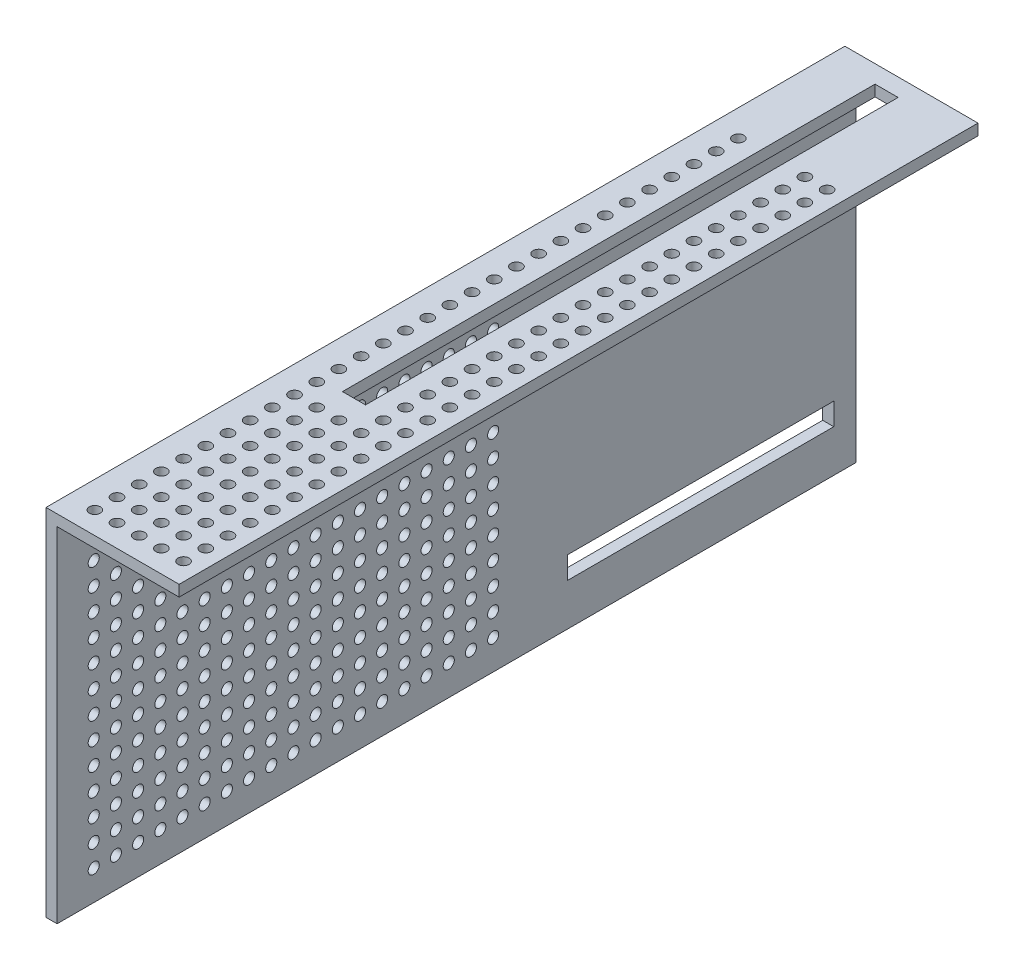
SolidWorks part; units mm, degrees
ref_plane "Front Plane" through (0, 0, 0) normal (0, 0, 1) x (1, 0, 0)
ref_plane "Top Plane" through (0, 0, 0) normal (0, 1, 0) x (1, 0, 0)
ref_plane "Right Plane" through (0, 0, 0) normal (1, 0, 0) x (0, 0, -1)
sketch "Sketch1" plane through (0, 0, 0) normal (0, 0, 1) x (1, 0, 0)
  line L0 (1.5875, 47.625) -> (36.5125, 47.625)
  line L1 (1.5875, -50.8) -> (-1.5875, -50.8)
  line L2 (1.5875, -50.8) -> (1.5875, 47.625)
  line L4 (-1.5875, -50.8) -> (-1.5875, 50.8)
  line L5 (1.5875, -50.8) -> (-1.5875, 50.8) construction
  line L6 (3.5127, 112.4075) -> (-1.5875, -50.8) construction
  line L7 (-1.5875, 50.8) -> (36.5125, 50.8)
  line L10 (36.5125, 50.8) -> (36.5125, 47.625)
  point P0 (0, 0)
  point P7 (0, -50.8)
  dimension "D1" = 3.175
  dimension "D2" = 3.175
  dimension "D3" = 38.1
  dimension "D4" = 101.6
extrude "Boss-Extrude1" add sketch "Sketch1" along normal blind 228.6
sketch "Sketch2" plane through (1.5875, 0, 0) normal (1, 0, 0) x (0, 0, -1)
  line L0 (-228.6, -29.4596) -> (0, 47.625) construction
  line L1 (-228.6, -50.8) -> (-228.6, 47.625) construction
  line L2 (-228.6, 47.625) -> (0, 47.625) construction
  line L3 (0, -50.8) -> (0, 47.625) construction
ref_plane "Plane1 - BACKBOARD PLANE" through (0, 42.7626, 14.4197) normal (0, -0.9476, -0.3195) x (0, 0.3195, -0.9476)
ref_plane "Plane1" through (0, -1.5875, 0) normal (0, -1, 0) x (-1, 0, 0)
sketch "Sketch3" plane through (-1.5875, 0, 0) normal (-1, 0, 0) x (0, 0, 1)
  line L0 (228.6, -50.8) -> (0, -50.8) construction
  line L1 (82.55, -32.385) -> (6.35, -32.385)
  line L2 (82.55, -32.385) -> (82.55, -38.735)
  line L3 (82.55, -38.735) -> (6.35, -38.735)
  line L4 (6.35, -32.385) -> (6.35, -38.735)
  line L5 (82.55, -32.385) -> (6.35, -38.735) construction
  line L6 (82.55, -38.735) -> (6.35, -32.385) construction
  line L7 (0, 50.8) -> (0, -50.8) construction
  line L18 (6.35, 33.1888) -> (82.55, 33.1888)
  line L19 (6.35, 33.1888) -> (6.35, 26.2472)
  line L20 (6.35, 26.2472) -> (82.55, 26.2472)
  line L21 (82.55, 33.1888) -> (82.55, 26.2472)
  point P0 (44.45, -35.56)
  point P13 (6.35, 29.718)
  point P14 (6.35, -35.56)
  dimension "D1" = 6.35
  dimension "D2" = 15.24
  dimension "D3" = 76.2
  dimension "D4" = 6.35
  dimension "D5" = 65.278
extrude "Cut-Extrude1" cut sketch "Sketch3" against normal up to next
sketch "Sketch4" plane through (-1.5875, 0, 0) normal (-1, 0, 0) x (0, 0, 1)
  circle A0 centre (103.8185, 40.3289) radius 1.5875
  circle A1 centre (110.1685, 40.3289) radius 1.5875
  circle A2 centre (116.5185, 40.3289) radius 1.5875
  circle A3 centre (122.8685, 40.3289) radius 1.5875
  circle A4 centre (129.2185, 40.3289) radius 1.5875
  circle A5 centre (110.1685, 33.9789) radius 1.5875
  circle A6 centre (116.5185, 33.9789) radius 1.5875
  circle A7 centre (122.8685, 33.9789) radius 1.5875
  circle A8 centre (129.2185, 33.9789) radius 1.5875
  circle A9 centre (110.1685, 27.6289) radius 1.5875
  circle A10 centre (116.5185, 27.6289) radius 1.5875
  circle A11 centre (122.8685, 27.6289) radius 1.5875
  circle A12 centre (129.2185, 27.6289) radius 1.5875
  circle A13 centre (110.1685, 21.2789) radius 1.5875
  circle A14 centre (116.5185, 21.2789) radius 1.5875
  circle A15 centre (122.8685, 21.2789) radius 1.5875
  circle A16 centre (129.2185, 21.2789) radius 1.5875
  circle A17 centre (103.8185, 33.9789) radius 1.5875
  circle A18 centre (103.8185, 27.6289) radius 1.5875
  circle A19 centre (103.8185, 21.2789) radius 1.5875
  circle A20 centre (135.5685, 40.3289) radius 1.5875
  circle A21 centre (141.9185, 40.3289) radius 1.5875
  circle A22 centre (148.2685, 40.3289) radius 1.5875
  circle A23 centre (154.6185, 40.3289) radius 1.5875
  circle A24 centre (160.9685, 40.3289) radius 1.5875
  circle A25 centre (167.3185, 40.3289) radius 1.5875
  circle A26 centre (173.6685, 40.3289) radius 1.5875
  circle A27 centre (180.0185, 40.3289) radius 1.5875
  circle A28 centre (186.3685, 40.3289) radius 1.5875
  circle A29 centre (192.7185, 40.3289) radius 1.5875
  circle A30 centre (199.0685, 40.3289) radius 1.5875
  circle A31 centre (205.4185, 40.3289) radius 1.5875
  circle A32 centre (211.7685, 40.3289) radius 1.5875
  circle A33 centre (218.1185, 40.3289) radius 1.5875
  circle A34 centre (135.5685, 33.9789) radius 1.5875
  circle A35 centre (141.9185, 33.9789) radius 1.5875
  circle A36 centre (148.2685, 33.9789) radius 1.5875
  circle A37 centre (154.6185, 33.9789) radius 1.5875
  circle A38 centre (160.9685, 33.9789) radius 1.5875
  circle A39 centre (167.3185, 33.9789) radius 1.5875
  circle A40 centre (173.6685, 33.9789) radius 1.5875
  circle A41 centre (180.0185, 33.9789) radius 1.5875
  circle A42 centre (186.3685, 33.9789) radius 1.5875
  circle A43 centre (192.7185, 33.9789) radius 1.5875
  circle A44 centre (199.0685, 33.9789) radius 1.5875
  circle A45 centre (205.4185, 33.9789) radius 1.5875
  circle A46 centre (211.7685, 33.9789) radius 1.5875
  circle A47 centre (218.1185, 33.9789) radius 1.5875
  circle A48 centre (135.5685, 27.6289) radius 1.5875
  circle A49 centre (141.9185, 27.6289) radius 1.5875
  circle A50 centre (148.2685, 27.6289) radius 1.5875
  circle A51 centre (154.6185, 27.6289) radius 1.5875
  circle A52 centre (160.9685, 27.6289) radius 1.5875
  circle A53 centre (167.3185, 27.6289) radius 1.5875
  circle A54 centre (173.6685, 27.6289) radius 1.5875
  circle A55 centre (180.0185, 27.6289) radius 1.5875
  circle A56 centre (186.3685, 27.6289) radius 1.5875
  circle A57 centre (192.7185, 27.6289) radius 1.5875
  circle A58 centre (199.0685, 27.6289) radius 1.5875
  circle A59 centre (205.4185, 27.6289) radius 1.5875
  circle A60 centre (211.7685, 27.6289) radius 1.5875
  circle A61 centre (218.1185, 27.6289) radius 1.5875
  circle A62 centre (135.5685, 21.2789) radius 1.5875
  circle A63 centre (141.9185, 21.2789) radius 1.5875
  circle A64 centre (148.2685, 21.2789) radius 1.5875
  circle A65 centre (154.6185, 21.2789) radius 1.5875
  circle A66 centre (160.9685, 21.2789) radius 1.5875
  circle A67 centre (167.3185, 21.2789) radius 1.5875
  circle A68 centre (173.6685, 21.2789) radius 1.5875
  circle A69 centre (180.0185, 21.2789) radius 1.5875
  circle A70 centre (186.3685, 21.2789) radius 1.5875
  circle A71 centre (192.7185, 21.2789) radius 1.5875
  circle A72 centre (199.0685, 21.2789) radius 1.5875
  circle A73 centre (205.4185, 21.2789) radius 1.5875
  circle A74 centre (211.7685, 21.2789) radius 1.5875
  circle A75 centre (218.1185, 21.2789) radius 1.5875
  circle A76 centre (103.8185, 14.9289) radius 1.5875
  circle A77 centre (110.1685, 14.9289) radius 1.5875
  circle A78 centre (116.5185, 14.9289) radius 1.5875
  circle A79 centre (122.8685, 14.9289) radius 1.5875
  circle A80 centre (129.2185, 14.9289) radius 1.5875
  circle A81 centre (135.5685, 14.9289) radius 1.5875
  circle A82 centre (141.9185, 14.9289) radius 1.5875
  circle A83 centre (148.2685, 14.9289) radius 1.5875
  circle A84 centre (154.6185, 14.9289) radius 1.5875
  circle A85 centre (160.9685, 14.9289) radius 1.5875
  circle A86 centre (167.3185, 14.9289) radius 1.5875
  circle A87 centre (173.6685, 14.9289) radius 1.5875
  circle A88 centre (180.0185, 14.9289) radius 1.5875
  circle A89 centre (186.3685, 14.9289) radius 1.5875
  circle A90 centre (192.7185, 14.9289) radius 1.5875
  circle A91 centre (199.0685, 14.9289) radius 1.5875
  circle A92 centre (205.4185, 14.9289) radius 1.5875
  circle A93 centre (211.7685, 14.9289) radius 1.5875
  circle A94 centre (218.1185, 14.9289) radius 1.5875
  circle A95 centre (103.8185, 8.5789) radius 1.5875
  circle A96 centre (110.1685, 8.5789) radius 1.5875
  circle A97 centre (116.5185, 8.5789) radius 1.5875
  circle A98 centre (122.8685, 8.5789) radius 1.5875
  circle A99 centre (129.2185, 8.5789) radius 1.5875
  circle A100 centre (135.5685, 8.5789) radius 1.5875
  circle A101 centre (141.9185, 8.5789) radius 1.5875
  circle A102 centre (148.2685, 8.5789) radius 1.5875
  circle A103 centre (154.6185, 8.5789) radius 1.5875
  circle A104 centre (160.9685, 8.5789) radius 1.5875
  circle A105 centre (167.3185, 8.5789) radius 1.5875
  circle A106 centre (173.6685, 8.5789) radius 1.5875
  circle A107 centre (180.0185, 8.5789) radius 1.5875
  circle A108 centre (186.3685, 8.5789) radius 1.5875
  circle A109 centre (192.7185, 8.5789) radius 1.5875
  circle A110 centre (199.0685, 8.5789) radius 1.5875
  circle A111 centre (205.4185, 8.5789) radius 1.5875
  circle A112 centre (211.7685, 8.5789) radius 1.5875
  circle A113 centre (218.1185, 8.5789) radius 1.5875
  circle A114 centre (103.8185, 2.2289) radius 1.5875
  circle A115 centre (110.1685, 2.2289) radius 1.5875
  circle A116 centre (116.5185, 2.2289) radius 1.5875
  circle A117 centre (122.8685, 2.2289) radius 1.5875
  circle A118 centre (129.2185, 2.2289) radius 1.5875
  circle A119 centre (135.5685, 2.2289) radius 1.5875
  circle A120 centre (141.9185, 2.2289) radius 1.5875
  circle A121 centre (148.2685, 2.2289) radius 1.5875
  circle A122 centre (154.6185, 2.2289) radius 1.5875
  circle A123 centre (160.9685, 2.2289) radius 1.5875
  circle A124 centre (167.3185, 2.2289) radius 1.5875
  circle A125 centre (173.6685, 2.2289) radius 1.5875
  circle A126 centre (180.0185, 2.2289) radius 1.5875
  circle A127 centre (186.3685, 2.2289) radius 1.5875
  circle A128 centre (192.7185, 2.2289) radius 1.5875
  circle A129 centre (199.0685, 2.2289) radius 1.5875
  circle A130 centre (205.4185, 2.2289) radius 1.5875
  circle A131 centre (211.7685, 2.2289) radius 1.5875
  circle A132 centre (218.1185, 2.2289) radius 1.5875
  circle A133 centre (103.8185, -4.1211) radius 1.5875
  circle A134 centre (110.1685, -4.1211) radius 1.5875
  circle A135 centre (116.5185, -4.1211) radius 1.5875
  circle A136 centre (122.8685, -4.1211) radius 1.5875
  circle A137 centre (129.2185, -4.1211) radius 1.5875
  circle A138 centre (135.5685, -4.1211) radius 1.5875
  circle A139 centre (141.9185, -4.1211) radius 1.5875
  circle A140 centre (148.2685, -4.1211) radius 1.5875
  circle A141 centre (154.6185, -4.1211) radius 1.5875
  circle A142 centre (160.9685, -4.1211) radius 1.5875
  circle A143 centre (167.3185, -4.1211) radius 1.5875
  circle A144 centre (173.6685, -4.1211) radius 1.5875
  circle A145 centre (180.0185, -4.1211) radius 1.5875
  circle A146 centre (186.3685, -4.1211) radius 1.5875
  circle A147 centre (192.7185, -4.1211) radius 1.5875
  circle A148 centre (199.0685, -4.1211) radius 1.5875
  circle A149 centre (205.4185, -4.1211) radius 1.5875
  circle A150 centre (211.7685, -4.1211) radius 1.5875
  circle A151 centre (218.1185, -4.1211) radius 1.5875
  circle A152 centre (103.8185, -10.4711) radius 1.5875
  circle A153 centre (110.1685, -10.4711) radius 1.5875
  circle A154 centre (116.5185, -10.4711) radius 1.5875
  circle A155 centre (122.8685, -10.4711) radius 1.5875
  circle A156 centre (129.2185, -10.4711) radius 1.5875
  circle A157 centre (135.5685, -10.4711) radius 1.5875
  circle A158 centre (141.9185, -10.4711) radius 1.5875
  circle A159 centre (148.2685, -10.4711) radius 1.5875
  circle A160 centre (154.6185, -10.4711) radius 1.5875
  circle A161 centre (160.9685, -10.4711) radius 1.5875
  circle A162 centre (167.3185, -10.4711) radius 1.5875
  circle A163 centre (173.6685, -10.4711) radius 1.5875
  circle A164 centre (180.0185, -10.4711) radius 1.5875
  circle A165 centre (186.3685, -10.4711) radius 1.5875
  circle A166 centre (192.7185, -10.4711) radius 1.5875
  circle A167 centre (199.0685, -10.4711) radius 1.5875
  circle A168 centre (205.4185, -10.4711) radius 1.5875
  circle A169 centre (211.7685, -10.4711) radius 1.5875
  circle A170 centre (218.1185, -10.4711) radius 1.5875
  circle A171 centre (103.8185, -16.8211) radius 1.5875
  circle A172 centre (110.1685, -16.8211) radius 1.5875
  circle A173 centre (116.5185, -16.8211) radius 1.5875
  circle A174 centre (122.8685, -16.8211) radius 1.5875
  circle A175 centre (129.2185, -16.8211) radius 1.5875
  circle A176 centre (135.5685, -16.8211) radius 1.5875
  circle A177 centre (141.9185, -16.8211) radius 1.5875
  circle A178 centre (148.2685, -16.8211) radius 1.5875
  circle A179 centre (154.6185, -16.8211) radius 1.5875
  circle A180 centre (160.9685, -16.8211) radius 1.5875
  circle A181 centre (167.3185, -16.8211) radius 1.5875
  circle A182 centre (173.6685, -16.8211) radius 1.5875
  circle A183 centre (180.0185, -16.8211) radius 1.5875
  circle A184 centre (186.3685, -16.8211) radius 1.5875
  circle A185 centre (192.7185, -16.8211) radius 1.5875
  circle A186 centre (199.0685, -16.8211) radius 1.5875
  circle A187 centre (205.4185, -16.8211) radius 1.5875
  circle A188 centre (211.7685, -16.8211) radius 1.5875
  circle A189 centre (218.1185, -16.8211) radius 1.5875
  circle A190 centre (103.8185, -23.1711) radius 1.5875
  circle A191 centre (110.1685, -23.1711) radius 1.5875
  circle A192 centre (116.5185, -23.1711) radius 1.5875
  circle A193 centre (122.8685, -23.1711) radius 1.5875
  circle A194 centre (129.2185, -23.1711) radius 1.5875
  circle A195 centre (135.5685, -23.1711) radius 1.5875
  circle A196 centre (141.9185, -23.1711) radius 1.5875
  circle A197 centre (148.2685, -23.1711) radius 1.5875
  circle A198 centre (154.6185, -23.1711) radius 1.5875
  circle A199 centre (160.9685, -23.1711) radius 1.5875
  circle A200 centre (167.3185, -23.1711) radius 1.5875
  circle A201 centre (173.6685, -23.1711) radius 1.5875
  circle A202 centre (180.0185, -23.1711) radius 1.5875
  circle A203 centre (186.3685, -23.1711) radius 1.5875
  circle A204 centre (192.7185, -23.1711) radius 1.5875
  circle A205 centre (199.0685, -23.1711) radius 1.5875
  circle A206 centre (205.4185, -23.1711) radius 1.5875
  circle A207 centre (211.7685, -23.1711) radius 1.5875
  circle A208 centre (218.1185, -23.1711) radius 1.5875
  circle A209 centre (103.8185, -29.5211) radius 1.5875
  circle A210 centre (110.1685, -29.5211) radius 1.5875
  circle A211 centre (116.5185, -29.5211) radius 1.5875
  circle A212 centre (122.8685, -29.5211) radius 1.5875
  circle A213 centre (129.2185, -29.5211) radius 1.5875
  circle A214 centre (135.5685, -29.5211) radius 1.5875
  circle A215 centre (141.9185, -29.5211) radius 1.5875
  circle A216 centre (148.2685, -29.5211) radius 1.5875
  circle A217 centre (154.6185, -29.5211) radius 1.5875
  circle A218 centre (160.9685, -29.5211) radius 1.5875
  circle A219 centre (167.3185, -29.5211) radius 1.5875
  circle A220 centre (173.6685, -29.5211) radius 1.5875
  circle A221 centre (180.0185, -29.5211) radius 1.5875
  circle A222 centre (186.3685, -29.5211) radius 1.5875
  circle A223 centre (192.7185, -29.5211) radius 1.5875
  circle A224 centre (199.0685, -29.5211) radius 1.5875
  circle A225 centre (205.4185, -29.5211) radius 1.5875
  circle A226 centre (211.7685, -29.5211) radius 1.5875
  circle A227 centre (218.1185, -29.5211) radius 1.5875
  circle A228 centre (103.8185, -35.8711) radius 1.5875
  circle A229 centre (110.1685, -35.8711) radius 1.5875
  circle A230 centre (116.5185, -35.8711) radius 1.5875
  circle A231 centre (122.8685, -35.8711) radius 1.5875
  circle A232 centre (129.2185, -35.8711) radius 1.5875
  circle A233 centre (135.5685, -35.8711) radius 1.5875
  circle A234 centre (141.9185, -35.8711) radius 1.5875
  circle A235 centre (148.2685, -35.8711) radius 1.5875
  circle A236 centre (154.6185, -35.8711) radius 1.5875
  circle A237 centre (160.9685, -35.8711) radius 1.5875
  circle A238 centre (167.3185, -35.8711) radius 1.5875
  circle A239 centre (173.6685, -35.8711) radius 1.5875
  circle A240 centre (180.0185, -35.8711) radius 1.5875
  circle A241 centre (186.3685, -35.8711) radius 1.5875
  circle A242 centre (192.7185, -35.8711) radius 1.5875
  circle A243 centre (199.0685, -35.8711) radius 1.5875
  circle A244 centre (205.4185, -35.8711) radius 1.5875
  circle A245 centre (211.7685, -35.8711) radius 1.5875
  circle A246 centre (218.1185, -35.8711) radius 1.5875
  circle A247 centre (103.8185, -42.2211) radius 1.5875
  circle A248 centre (110.1685, -42.2211) radius 1.5875
  circle A249 centre (116.5185, -42.2211) radius 1.5875
  circle A250 centre (122.8685, -42.2211) radius 1.5875
  circle A251 centre (129.2185, -42.2211) radius 1.5875
  circle A252 centre (135.5685, -42.2211) radius 1.5875
  circle A253 centre (141.9185, -42.2211) radius 1.5875
  circle A254 centre (148.2685, -42.2211) radius 1.5875
  circle A255 centre (154.6185, -42.2211) radius 1.5875
  circle A256 centre (160.9685, -42.2211) radius 1.5875
  circle A257 centre (167.3185, -42.2211) radius 1.5875
  circle A258 centre (173.6685, -42.2211) radius 1.5875
  circle A259 centre (180.0185, -42.2211) radius 1.5875
  circle A260 centre (186.3685, -42.2211) radius 1.5875
  circle A261 centre (192.7185, -42.2211) radius 1.5875
  circle A262 centre (199.0685, -42.2211) radius 1.5875
  circle A263 centre (205.4185, -42.2211) radius 1.5875
  circle A264 centre (211.7685, -42.2211) radius 1.5875
  circle A265 centre (218.1185, -42.2211) radius 1.5875
  dimension "D1" = 3.175
  dimension "D2" = 19
  dimension "D3" = 14
extrude "Cut-Extrude2" cut sketch "Sketch4" against normal up to next (3.175 mm away)
sketch "Sketch5" plane through (0, 50.8, 0) normal (0, 1, 0) x (1, 0, 0)
  line L0 (36.5125, 0) -> (-1.5875, 0) construction
  line L1 (18.7325, -5.08) -> (12.1285, -5.08)
  line L2 (18.7325, -5.08) -> (18.7325, -157.48)
  line L3 (18.7325, -157.48) -> (12.1285, -157.48)
  line L4 (12.1285, -5.08) -> (12.1285, -157.48)
  line L5 (36.5125, -228.6) -> (36.5125, 0) construction
  point P8 (15.4305, -5.08)
  dimension "D1" = 6.604
  dimension "D2" = 152.4
  dimension "D3" = 5.08
  dimension "D4" = 21.082
extrude "Cut-Extrude3" cut sketch "Sketch5" against normal up to next
sketch "Sketch6" plane through (0, 50.8, 0) normal (0, 1, 0) x (1, 0, 0)
  line L0 (36.5125, -228.6) -> (-1.5875, -228.6) construction
  line L1 (36.5125, -228.6) -> (36.5125, 0) construction
  circle A0 centre (6.0325, -222.25) radius 1.5875
  circle A1 centre (12.3825, -222.25) radius 1.5875
  circle A2 centre (18.7325, -222.25) radius 1.5875
  circle A3 centre (25.0825, -222.25) radius 1.5875
  circle A4 centre (31.4325, -222.25) radius 1.5875
  circle A5 centre (12.3825, -215.9) radius 1.5875
  circle A6 centre (18.7325, -215.9) radius 1.5875
  circle A7 centre (25.0825, -215.9) radius 1.5875
  circle A8 centre (31.4325, -215.9) radius 1.5875
  circle A9 centre (12.3825, -209.55) radius 1.5875
  circle A10 centre (18.7325, -209.55) radius 1.5875
  circle A11 centre (25.0825, -209.55) radius 1.5875
  circle A12 centre (31.4325, -209.55) radius 1.5875
  circle A13 centre (12.3825, -203.2) radius 1.5875
  circle A14 centre (18.7325, -203.2) radius 1.5875
  circle A15 centre (25.0825, -203.2) radius 1.5875
  circle A16 centre (31.4325, -203.2) radius 1.5875
  circle A17 centre (12.3825, -196.85) radius 1.5875
  circle A18 centre (18.7325, -196.85) radius 1.5875
  circle A19 centre (25.0825, -196.85) radius 1.5875
  circle A20 centre (31.4325, -196.85) radius 1.5875
  circle A21 centre (12.3825, -190.5) radius 1.5875
  circle A22 centre (18.7325, -190.5) radius 1.5875
  circle A23 centre (25.0825, -190.5) radius 1.5875
  circle A24 centre (31.4325, -190.5) radius 1.5875
  circle A25 centre (12.3825, -184.15) radius 1.5875
  circle A26 centre (18.7325, -184.15) radius 1.5875
  circle A27 centre (25.0825, -184.15) radius 1.5875
  circle A28 centre (31.4325, -184.15) radius 1.5875
  circle A29 centre (12.3825, -177.8) radius 1.5875
  circle A30 centre (18.7325, -177.8) radius 1.5875
  circle A31 centre (25.0825, -177.8) radius 1.5875
  circle A32 centre (31.4325, -177.8) radius 1.5875
  circle A33 centre (12.3825, -171.45) radius 1.5875
  circle A34 centre (18.7325, -171.45) radius 1.5875
  circle A35 centre (25.0825, -171.45) radius 1.5875
  circle A36 centre (31.4325, -171.45) radius 1.5875
  circle A37 centre (12.3825, -165.1) radius 1.5875
  circle A38 centre (18.7325, -165.1) radius 1.5875
  circle A39 centre (25.0825, -165.1) radius 1.5875
  circle A40 centre (31.4325, -165.1) radius 1.5875
  circle A43 centre (25.0825, -158.75) radius 1.5875
  circle A44 centre (31.4325, -158.75) radius 1.5875
  circle A47 centre (25.0825, -152.4) radius 1.5875
  circle A48 centre (31.4325, -152.4) radius 1.5875
  circle A51 centre (25.0825, -146.05) radius 1.5875
  circle A52 centre (31.4325, -146.05) radius 1.5875
  circle A55 centre (25.0825, -139.7) radius 1.5875
  circle A56 centre (31.4325, -139.7) radius 1.5875
  circle A59 centre (25.0825, -133.35) radius 1.5875
  circle A60 centre (31.4325, -133.35) radius 1.5875
  circle A63 centre (25.0825, -127) radius 1.5875
  circle A64 centre (31.4325, -127) radius 1.5875
  circle A67 centre (25.0825, -120.65) radius 1.5875
  circle A68 centre (31.4325, -120.65) radius 1.5875
  circle A71 centre (25.0825, -114.3) radius 1.5875
  circle A72 centre (31.4325, -114.3) radius 1.5875
  circle A75 centre (25.0825, -107.95) radius 1.5875
  circle A76 centre (31.4325, -107.95) radius 1.5875
  circle A79 centre (25.0825, -101.6) radius 1.5875
  circle A80 centre (31.4325, -101.6) radius 1.5875
  circle A83 centre (25.0825, -95.25) radius 1.5875
  circle A84 centre (31.4325, -95.25) radius 1.5875
  circle A87 centre (25.0825, -88.9) radius 1.5875
  circle A88 centre (31.4325, -88.9) radius 1.5875
  circle A91 centre (25.0825, -82.55) radius 1.5875
  circle A92 centre (31.4325, -82.55) radius 1.5875
  circle A95 centre (25.0825, -76.2) radius 1.5875
  circle A96 centre (31.4325, -76.2) radius 1.5875
  circle A99 centre (25.0825, -69.85) radius 1.5875
  circle A100 centre (31.4325, -69.85) radius 1.5875
  circle A103 centre (25.0825, -63.5) radius 1.5875
  circle A104 centre (31.4325, -63.5) radius 1.5875
  circle A107 centre (25.0825, -57.15) radius 1.5875
  circle A108 centre (31.4325, -57.15) radius 1.5875
  circle A111 centre (25.0825, -50.8) radius 1.5875
  circle A112 centre (31.4325, -50.8) radius 1.5875
  circle A115 centre (25.0825, -44.45) radius 1.5875
  circle A116 centre (31.4325, -44.45) radius 1.5875
  circle A119 centre (25.0825, -38.1) radius 1.5875
  circle A120 centre (31.4325, -38.1) radius 1.5875
  circle A121 centre (6.0325, -215.9) radius 1.5875
  circle A122 centre (6.0325, -209.55) radius 1.5875
  circle A123 centre (6.0325, -203.2) radius 1.5875
  circle A124 centre (6.0325, -196.85) radius 1.5875
  circle A125 centre (6.0325, -190.5) radius 1.5875
  circle A126 centre (6.0325, -184.15) radius 1.5875
  circle A127 centre (6.0325, -177.8) radius 1.5875
  circle A128 centre (6.0325, -171.45) radius 1.5875
  circle A129 centre (6.0325, -165.1) radius 1.5875
  circle A130 centre (6.0325, -158.75) radius 1.5875
  circle A131 centre (6.0325, -152.4) radius 1.5875
  circle A132 centre (6.0325, -146.05) radius 1.5875
  circle A133 centre (6.0325, -139.7) radius 1.5875
  circle A134 centre (6.0325, -133.35) radius 1.5875
  circle A135 centre (6.0325, -127) radius 1.5875
  circle A136 centre (6.0325, -120.65) radius 1.5875
  circle A137 centre (6.0325, -114.3) radius 1.5875
  circle A138 centre (6.0325, -107.95) radius 1.5875
  circle A139 centre (6.0325, -101.6) radius 1.5875
  circle A140 centre (6.0325, -95.25) radius 1.5875
  circle A141 centre (6.0325, -88.9) radius 1.5875
  circle A142 centre (6.0325, -82.55) radius 1.5875
  circle A143 centre (6.0325, -76.2) radius 1.5875
  circle A144 centre (6.0325, -69.85) radius 1.5875
  circle A145 centre (6.0325, -63.5) radius 1.5875
  circle A146 centre (6.0325, -57.15) radius 1.5875
  circle A147 centre (6.0325, -50.8) radius 1.5875
  circle A148 centre (6.0325, -44.45) radius 1.5875
  circle A149 centre (6.0325, -38.1) radius 1.5875
  circle A150 centre (18.7325, -50.8) radius 1.5875 [skipped]
  circle A151 centre (12.3825, -44.45) radius 1.5875 [skipped]
  circle A152 centre (18.7325, -44.45) radius 1.5875 [skipped]
  circle A153 centre (12.3825, -38.1) radius 1.5875 [skipped]
  circle A154 centre (18.7325, -38.1) radius 1.5875 [skipped]
  circle A155 centre (12.3825, -63.5) radius 1.5875 [skipped]
  circle A156 centre (18.7325, -63.5) radius 1.5875 [skipped]
  circle A157 centre (12.3825, -57.15) radius 1.5875 [skipped]
  circle A158 centre (18.7325, -57.15) radius 1.5875 [skipped]
  circle A159 centre (12.3825, -50.8) radius 1.5875 [skipped]
  circle A160 centre (12.3825, -158.75) radius 1.5875 [skipped]
  circle A161 centre (18.7325, -158.75) radius 1.5875 [skipped]
  circle A162 centre (12.3825, -152.4) radius 1.5875 [skipped]
  circle A163 centre (18.7325, -152.4) radius 1.5875 [skipped]
  circle A164 centre (12.3825, -146.05) radius 1.5875 [skipped]
  circle A165 centre (18.7325, -146.05) radius 1.5875 [skipped]
  circle A166 centre (12.3825, -139.7) radius 1.5875 [skipped]
  circle A167 centre (18.7325, -139.7) radius 1.5875 [skipped]
  circle A168 centre (12.3825, -133.35) radius 1.5875 [skipped]
  circle A169 centre (18.7325, -133.35) radius 1.5875 [skipped]
  circle A170 centre (12.3825, -127) radius 1.5875 [skipped]
  circle A171 centre (18.7325, -127) radius 1.5875 [skipped]
  circle A172 centre (12.3825, -120.65) radius 1.5875 [skipped]
  circle A173 centre (18.7325, -120.65) radius 1.5875 [skipped]
  circle A174 centre (12.3825, -114.3) radius 1.5875 [skipped]
  circle A175 centre (18.7325, -114.3) radius 1.5875 [skipped]
  circle A176 centre (12.3825, -107.95) radius 1.5875 [skipped]
  circle A177 centre (18.7325, -107.95) radius 1.5875 [skipped]
  circle A178 centre (12.3825, -101.6) radius 1.5875 [skipped]
  circle A179 centre (18.7325, -101.6) radius 1.5875 [skipped]
  circle A180 centre (12.3825, -95.25) radius 1.5875 [skipped]
  circle A181 centre (18.7325, -95.25) radius 1.5875 [skipped]
  circle A182 centre (12.3825, -88.9) radius 1.5875 [skipped]
  circle A183 centre (18.7325, -88.9) radius 1.5875 [skipped]
  circle A184 centre (12.3825, -82.55) radius 1.5875 [skipped]
  circle A185 centre (18.7325, -82.55) radius 1.5875 [skipped]
  circle A186 centre (12.3825, -76.2) radius 1.5875 [skipped]
  circle A187 centre (18.7325, -76.2) radius 1.5875 [skipped]
  circle A188 centre (12.3825, -69.85) radius 1.5875 [skipped]
  circle A189 centre (18.7325, -69.85) radius 1.5875 [skipped]
  dimension "D1" = 3.175
  dimension "D2" = 6.35
  dimension "D3" = 30.48
  dimension "D4" = 5
  dimension "D5" = 30
extrude "Cut-Extrude4" cut sketch "Sketch6" against normal up to next (3.175 mm away)
ref_plane "Plane2" through (1.5875, 0, 0) normal (1, 0, 0) x (0, 0, -1)
equation "\"eighthinch\"= 0.125"
equation "\"D2@Sketch1\"=\"eighthinch\""
